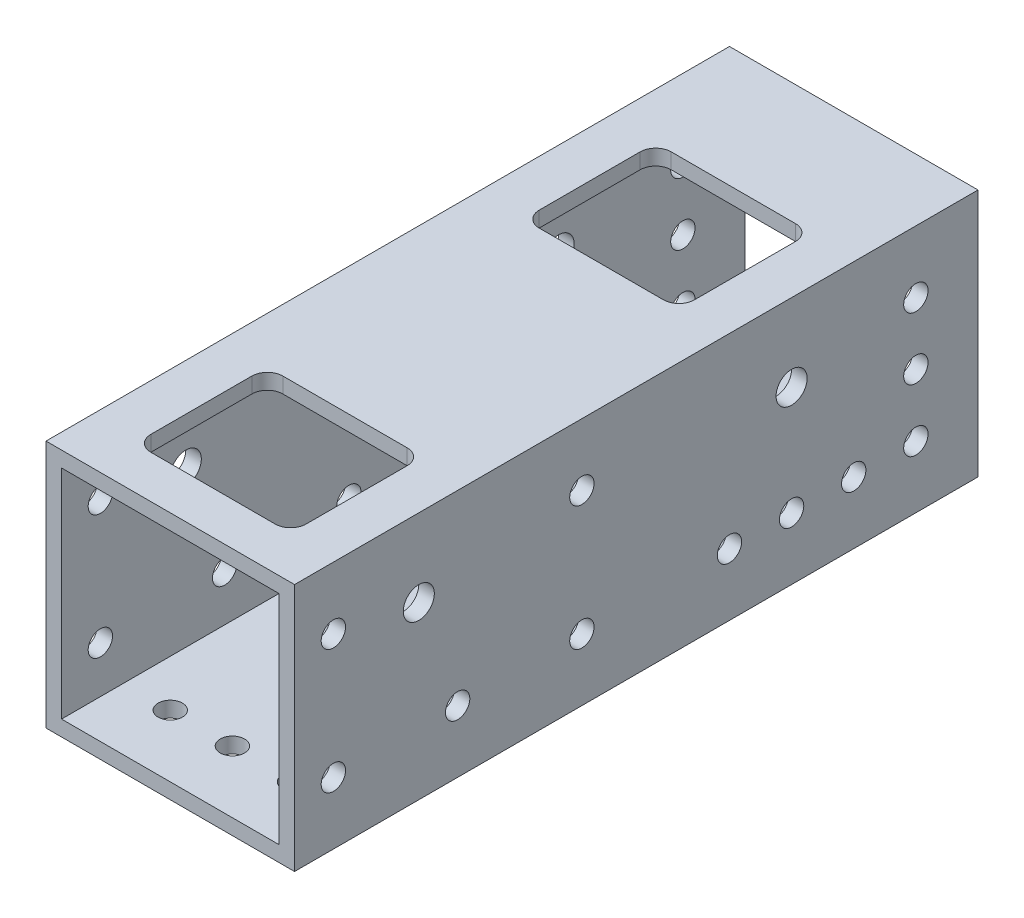
SolidWorks part; units mm, degrees
material "6061-T6 (SS)"
ref_plane "Front Plane" through (0, 0, 0) normal (0, 0, 1) x (1, 0, 0)
ref_plane "Top Plane" through (0, 0, 0) normal (0, 1, 0) x (1, 0, 0)
ref_plane "Right Plane" through (0, 0, 0) normal (1, 0, 0) x (0, 0, -1)
sketch "Sketch1" plane through (0, 0, 0) normal (0, 0, 1) x (1, 0, 0)
  line L1 (-25.4, -25.4) -> (25.4, -25.4)
  line L2 (-25.4, -25.4) -> (-25.4, 25.4)
  line L3 (-25.4, 25.4) -> (25.4, 25.4)
  line L4 (25.4, -25.4) -> (25.4, 25.4)
  line L5 (-25.4, -25.4) -> (25.4, 25.4) construction
  line L6 (-25.4, 25.4) -> (25.4, -25.4) construction
  point P0 (0, 0)
  dimension "D1" = 50.8
  dimension "D2" = 50.8
extrude "Boss-Extrude1" add sketch "Sketch1" along normal mid plane 139.7
shell "Shell1" thickness 3.175 removed face at (0, 0, -69.85) removed face at (0, 0, 69.85)
sketch "Sketch2" plane through (0, 0, 0) normal (0, 1, 0) x (1, 0, 0)
  line L0 (25.4, 69.85) -> (-25.4, 69.85) construction
  line L1 (15.875, 45.2437) -> (-15.875, 45.2437)
  line L2 (15.875, 45.2437) -> (15.875, 18.2563)
  line L3 (15.875, 18.2563) -> (-15.875, 18.2563)
  line L4 (-15.875, 45.2437) -> (-15.875, 18.2563)
  line L5 (25.4, -69.85) -> (-25.4, -69.85) construction
  line L7 (15.875, -34.1313) -> (-15.875, -34.1313)
  line L8 (15.875, -34.1313) -> (15.875, -61.1187)
  line L9 (15.875, -61.1187) -> (-15.875, -61.1187)
  line L10 (-15.875, -34.1313) -> (-15.875, -61.1187)
  point P4 (0, 45.2437)
  point P7 (0, 69.85)
  point P9 (15.875, 31.75)
  point P15 (0, -69.85)
  point P16 (0, -61.1187)
  point P17 (-15.875, -47.625)
  dimension "D1" = 31.75
  dimension "D2" = 26.9875
  dimension "D3" = 101.6
  dimension "D4" = 22.225
extrude "Cut-Extrude1" cut sketch "Sketch2" along normal through all
fillet "Fillet1" radius 3.175 4 edges at (15.875, 23.8125, -45.2437) (-15.875, 23.8125, -45.2437) (-15.875, 23.8125, -18.2563) (15.875, 23.8125, -18.2563)
sketch "Sketch3" plane through (0, 0, 0) normal (1, 0, 0) x (0, 0, -1)
  line L1 (-69.85, 25.4) -> (-69.85, -25.4) construction
  line L2 (-69.85, 25.4) -> (69.85, 25.4) construction
  circle A0 centre (31.75, 9.525) radius 3.175
  circle A1 centre (-44.45, 9.525) radius 3.175
  dimension "D1" = 6.35
  dimension "D2" = 25.4
  dimension "D3" = 76.2
  dimension "D4" = 15.875
extrude "Cut-Extrude2" cut sketch "Sketch3" against normal through all both and the other way through all
sketch "Sketch4" plane through (0, 0, 0) normal (1, 0, 0) x (0, 0, -1)
  line L0 (-69.85, 25.4) -> (69.85, 25.4) construction
  line L1 (69.85, 25.4) -> (69.85, -25.4) construction
  line L2 (-69.85, 25.4) -> (-69.85, -25.4) construction
  circle A0 centre (57.15, 12.7) radius 2.4892
  circle A1 centre (44.45, 12.7) radius 2.4892 construction
  circle A2 centre (31.75, 12.7) radius 2.4892 construction
  circle A3 centre (19.05, 12.7) radius 2.4892 construction
  circle A10 centre (44.45, 0) radius 2.4892 construction
  circle A11 centre (31.75, 0) radius 2.4892 construction
  circle A12 centre (19.05, 0) radius 2.4892 construction
  circle A19 centre (44.45, -12.7) radius 2.4892
  circle A20 centre (31.75, -12.7) radius 2.4892
  circle A21 centre (19.05, -12.7) radius 2.4892
  circle A28 centre (57.15, 0) radius 2.4892
  circle A29 centre (57.15, -12.7) radius 2.4892
  circle A30 centre (-61.9125, 12.7) radius 2.4892
  circle A31 centre (-49.2125, 12.7) radius 2.4892 construction
  circle A32 centre (-36.5125, 12.7) radius 2.4892 construction
  circle A33 centre (-23.8125, 12.7) radius 2.4892 construction
  circle A34 centre (-11.1125, 12.7) radius 2.4892
  circle A35 centre (1.5875, 12.7) radius 2.4892 construction
  circle A36 centre (-49.2125, 0) radius 2.4892 construction
  circle A37 centre (-36.5125, 0) radius 2.4892 construction
  circle A38 centre (-23.8125, 0) radius 2.4892 construction
  circle A39 centre (-11.1125, 0) radius 2.4892 construction
  circle A40 centre (1.5875, 0) radius 2.4892 construction
  circle A41 centre (-49.2125, -12.7) radius 2.4892 construction
  circle A42 centre (-36.5125, -12.7) radius 2.4892
  circle A43 centre (-23.8125, -12.7) radius 2.4892 construction
  circle A44 centre (-11.1125, -12.7) radius 2.4892
  circle A45 centre (1.5875, -12.7) radius 2.4892 construction
  circle A46 centre (-61.9125, 0) radius 2.4892 construction
  circle A47 centre (-61.9125, -12.7) radius 2.4892
  dimension "D1" = 4.9784
  dimension "D3" = 12.7
  dimension "D8" = 4.9784
  dimension "D9" = 7.9375
  dimension "D14" = 12.7
  dimension "D2" = 12.7
  dimension "D6" = 12.7
  dimension "D7" = 12.7
  dimension "D10" = 12.7
  dimension "D13" = 12.7
  dimension "D4" = 4
  dimension "D5" = 3
  dimension "D11" = 6
  dimension "D12" = 3
extrude "Cut-Extrude3" cut sketch "Sketch4" against normal through all both and the other way through all
sketch "Sketch5" plane through (0, 0, 0) normal (0, 1, 0) x (1, 0, 0)
  line L1 (25.4, -69.85) -> (-25.4, -69.85) construction
  line L2 (-25.4, -69.85) -> (-25.4, 69.85) construction
  circle A0 centre (-12.7, -57.15) radius 2.4892
  circle A1 centre (0, -57.15) radius 2.4892
  circle A2 centre (12.7, -57.15) radius 2.4892
  dimension "D1" = 4.9784
  dimension "D3" = 12.7
  dimension "D2" = 12.7
  dimension "D5" = 12.7
  dimension "D4" = 3
extrude "Cut-Extrude4" cut sketch "Sketch5" against normal through all and the other way through all
fillet "Fillet2" radius 3.175 4 edges at (-15.875, 23.8125, 34.1313) (-15.875, 23.8125, 61.1187) (15.875, 23.8125, 61.1187) (15.875, 23.8125, 34.1313)
